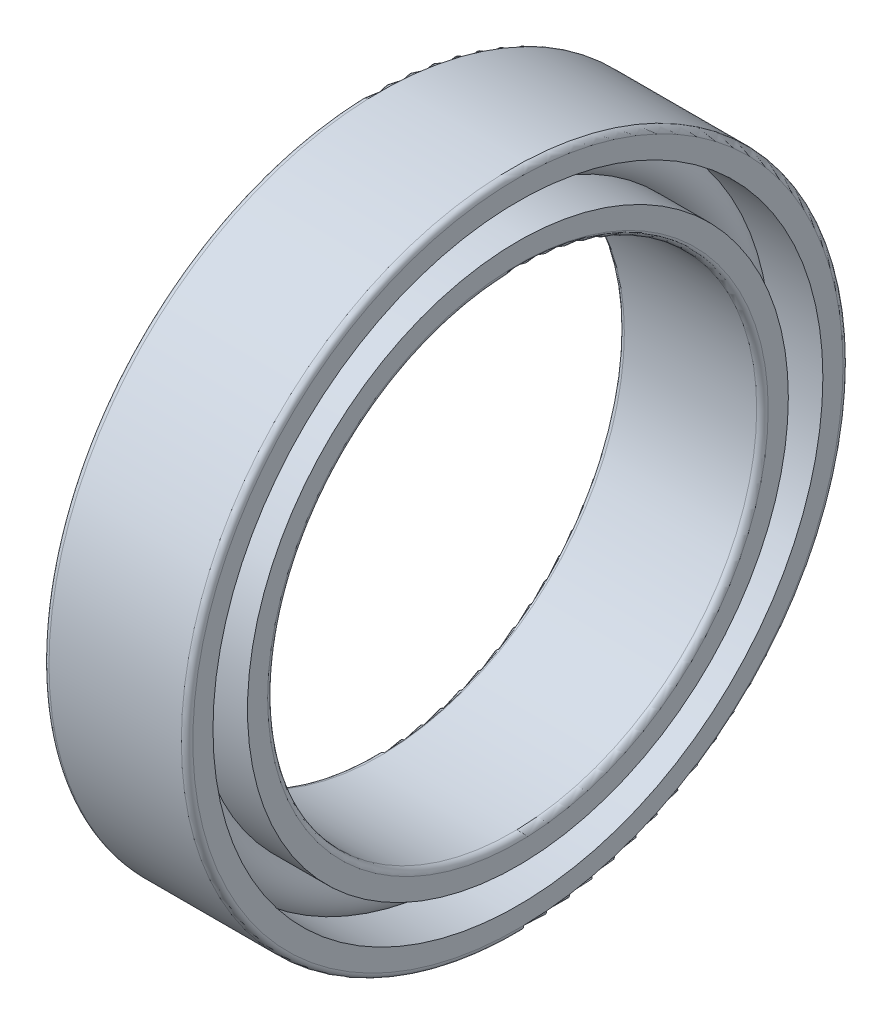
SolidWorks part; units mm, degrees
ref_plane "Plane1" through (0, 0, 0) normal (0, 0, 1) x (1, 0, 0)
ref_plane "Plane2" through (0, 0, 0) normal (0, 1, 0) x (1, 0, 0)
ref_plane "Plane3" through (0, 0, 0) normal (1, 0, 0) x (0, 0, -1)
other "Configuration Table"
sketch "Clipboard" plane through (0, 0, 0) normal (0, 0, 1) x (1, 0, 0)
  line L0 (-10, 0) -> (10, 0) construction
  line L1 (0, 0) -> (22.3471, -0.7804)
  line L2 (0, 0) -> (9.9939, 0.349)
  line L3 (0, 0) -> (22.3471, -0.7804)
  line L4 (0, 0) -> (-22.3573, -0.3902)
  dimension "BallCLRad" = 10
  dimension "Count" = 2
sketch "CagSpiSke" plane through (0, 0, 0) normal (0, 0, 1) x (1, 0, 0)
  line L0 (0.09, 9.85) -> (0.09, 10.15)
  line L1 (0.09, 10.15) -> (-0.09, 10.15)
  line L2 (-0.09, 10.15) -> (-0.09, 9.85)
  line L3 (-0.09, 9.85) -> (0.09, 9.85)
  line L4 (-20.6375, 0) -> (20.6375, 0) construction
  line L5 (0, 0) -> (0, 23.7692) construction
  dimension "OD" = 20.3
  dimension "ID" = 19.7
revolve "CageSpine" add sketch "CagSpiSke" angle 0.001 about L4 reverse direction yes
ref_axis "Axis1" through (-50, 0, 0) along (1, 0, 0)
sketch "CagBalSke" plane through (0, 0, 0) normal (0, 0, 1) x (1, 0, 0)
  line L0 (-0.99, 10) -> (0.99, 10)
  line L1 (-1.905, 10) -> (1.905, 10) construction
  line L2 (-10, 0) -> (10, 0) construction
  line L3 (0, 0) -> (0, 24) construction
  arc A0 (0.99, 10) -> (-0.99, 10) centre (0, 10) cw
  dimension "BallCLRad" = 10
revolve "CageBall" [suppressed] add sketch "CagBalSke" angle 360 about L1 reverse direction yes
pattern_circular "CageBalls" [suppressed] count 2 every 180 about axis through (-50, 0, 0) along (1, 0, 0)
sketch "CagTrmODSke" plane through (0, 0, 0) normal (0, 0, 1) x (1, 0, 0)
  line L0 (0.991, 10.15) -> (0.991, 10.991)
  line L1 (0.991, 10.991) -> (-0.991, 10.991)
  line L2 (-0.991, 10.991) -> (-0.991, 10.15)
  line L3 (-0.991, 10.15) -> (0.991, 10.15)
  line L4 (-20.6375, 0) -> (20.6375, 0) construction
  line L5 (0, 0) -> (0, 25) construction
  dimension "Width" = 1.982
  dimension "ID" = 20.3
  dimension "OD" = 21.982
revolve "CageTrimOD" [suppressed] cut sketch "CagTrmODSke" angle 360 about L4 reverse direction yes
sketch "CagTrmIDSke" plane through (0, 0, 0) normal (0, 0, 1) x (1, 0, 0)
  line L0 (0.991, 9.011) -> (0.991, 9.85)
  line L1 (0.991, 9.85) -> (-0.991, 9.85)
  line L2 (-0.991, 9.85) -> (-0.991, 9.011)
  line L3 (-0.991, 9.011) -> (0.991, 9.011)
  line L4 (-20.6375, 0) -> (20.6375, 0) construction
  line L5 (0, 0) -> (0, 25) construction
  dimension "Width" = 1.982
  dimension "ID" = 18.022
  dimension "OD" = 19.7
revolve "CageTrimID" [suppressed] cut sketch "CagTrmIDSke" angle 360 about L4 reverse direction yes
sketch "BalSimSke" plane through (0, 0, 0) normal (0, 0, 1) x (1, 0, 0)
  line L0 (-10, 0) -> (10, 0) construction
  line L1 (-10, 10) -> (10, 10) construction
  line L2 (0, 0) -> (0, 23) construction
  circle A0 centre (0, 10) radius 0.9
  dimension "BallCLRad" = 10
revolve "BallsSimplified" add sketch "BalSimSke" angle 360 about L0
sketch "BalDetSke" plane through (0, 0, 0) normal (0, 0, 1) x (1, 0, 0)
  line L0 (-0.9, 10) -> (0.9, 10)
  line L1 (-1.905, 10) -> (1.905, 10) construction
  line L2 (0, 0) -> (0, 25) construction
  arc A0 (0.9, 10) -> (-0.9, 10) centre (0, 10) cw
  dimension "BallCLRad" = 10
revolve "BallDetailed" [suppressed] add sketch "BalDetSke" angle 360 about L1 reverse direction yes
sketch "InnRacSke" plane through (0, 0, 0) normal (0, 0, 1) x (1, 0, 0)
  line L0 (-0.6369, 9.4) -> (-2.5, 9.4)
  line L1 (-2.5, 9.4) -> (-2.5, 8.7)
  line L2 (-2.3, 8.5) -> (2.3, 8.5)
  line L3 (2.5, 8.7) -> (2.5, 9.4)
  line L4 (2.5, 9.4) -> (0.6369, 9.4)
  line L5 (-20.6375, 0) -> (20.6375, 0) construction
  line L6 (0, 0) -> (0, 30) construction
  arc A0 (-2.5, 8.7) -> (-2.3, 8.5) centre (-2.3, 8.7) ccw
  arc A1 (2.3, 8.5) -> (2.5, 8.7) centre (2.3, 8.7) ccw
  arc A2 (0.6369, 9.4) -> (-0.6369, 9.4) centre (0, 10) cw
  dimension "BallCLRad" = 10
  dimension "Fillet_radius" = 0.2
  dimension "Ball_diameter" = 1.75
  dimension "ID" = 17
  dimension "OD" = 18.8
  dimension "Width" = 5
revolve "InnerRace" add sketch "InnRacSke" angle 360 about L5 reverse direction yes
sketch "OutRacSke" plane through (0, 0, 0) normal (0, 0, 1) x (1, 0, 0)
  line L0 (-0.6369, 10.6) -> (-2.5, 10.6)
  line L1 (-2.5, 10.6) -> (-2.5, 11.3)
  line L2 (-2.3, 11.5) -> (2.3, 11.5)
  line L3 (2.5, 11.3) -> (2.5, 10.6)
  line L4 (2.5, 10.6) -> (0.6369, 10.6)
  line L5 (-20.6375, 0) -> (20.6375, 0) construction
  line L6 (0, 0) -> (0, 30) construction
  arc A0 (-2.5, 11.3) -> (-2.3, 11.5) centre (-2.3, 11.3) cw
  arc A1 (2.3, 11.5) -> (2.5, 11.3) centre (2.3, 11.3) cw
  arc A2 (0.6369, 10.6) -> (-0.6369, 10.6) centre (0, 10) ccw
  dimension "BallCLRad" = 10
  dimension "Fillet_radius" = 0.2
  dimension "Ball_diameter" = 1.75
  dimension "Width" = 5
revolve "OuterRace" add sketch "OutRacSke" angle 360 about L5 reverse direction yes
pattern_circular "BallsDetailed" [suppressed] count 2 every 180 about axis through (-50, 0, 0) along (1, 0, 0)
equation "\"BallCLRad@Clipboard\" = ( \"OD@OutRacSke\" + \"ID@InnRacSke\" ) / 4"
equation "\"BallCLRad@BalSimSke\" = \"BallCLRad@Clipboard\""
equation "\"BallCLRad@BalDetSke\" = \"BallCLRad@Clipboard\""
equation "\"BallCLRad@InnRacSke\" = \"BallCLRad@Clipboard\""
equation "\"BallCLRad@OutRacSke\" = \"BallCLRad@Clipboard\""
equation "\"Ball_diameter@InnRacSke\" = \"Ball_diameter@BalDetSke\" - 0.05"
equation "\"Ball_diameter@OutRacSke\" = \"Ball_diameter@BalDetSke\" - 0.05"
equation "\"Ball_diameter@BalSimSke\" = \"Ball_diameter@BalDetSke\""
equation "\"Width@OutRacSke\" = \"Width@InnRacSke\""
equation "\"Fillet_radius@OutRacSke\" = \"Fillet_radius@InnRacSke\""
equation "\"Max_count@Clipboard\" = int( 3.14159265 / atn(( \"Ball_diameter@BalDetSke\" / 2) / sqr( \"BallCLRad@Clipboard\"  *  \"BallCLRad@Clipboard\" - ( \"Ball_diameter@BalDetSke\" / 2) *  ( \"Ball_diameter@BalDetSke\" / 2))))"
equation "\"Max_count@Clipboard\" = ((sgn( \"Max_count@Clipboard\" - \"Count@Clipboard\" )-1)*( \"Max_count@Clipboard\" - \"Count@Clipboard\" ))/-2+ \"Count@Clipboard\""
equation "\"Count@BallsDetailed\" = int( \"Show_count@Clipboard\" ) "
equation "\"Count@BallsDetailed\" = ((sgn( \"Count@BallsDetailed\" - \"Max_count@Clipboard\" )-1)*( \"Count@BallsDetailed\" - \"Max_count@Clipboard\" ))/-2+ \"Max_count@Clipboard\""
equation "\"Count@BallsDetailed\" = ((sgn( \"Count@BallsDetailed\" - \"Min_count@Clipboard\" )+1)*( \"Count@BallsDetailed\" - \"Min_count@Clipboard\"))/2 +\"Min_count@Clipboard\""
equation "\"Angle@BallsDetailed\" = 360.0 / \"Max_count@Clipboard\""
equation "\"BallCLRad@CagBalSke\" = \"BallCLRad@Clipboard\""
equation "\"Count@CageBalls\" = \"Count@BallsDetailed\""
equation "\"Angle@CageBalls\" = \"Angle@BallsDetailed\""
equation "\"Angle@CageSpine\" =  \"Angle@CageBalls\" * ( \"Count@CageBalls\" -1 + int( \"Count@CageBalls\" / \"Max_count@Clipboard\" ) )  + 0.001 -  int( \"Count@CageBalls\" / \"Max_count@Clipboard\" ) * 0.001"
equation "\"Angle@CageSpine\" =  \"Angle@CageSpine\" * int( \"Min_count@Clipboard\" / 2) + int(1 / \"Min_count@Clipboard\")  * 0.001"
equation "\"CageWallOD@CagBalSke\" =  \"Ball_diameter@BalDetSke\" * 1.1"
equation "\"Thickness@CagSpiSke\" =  \"Ball_diameter@BalDetSke\" * 0.1"
equation "\"OD@CagTrmODSke\" = \"BallCLRad@Clipboard\" * 2 + \"CageWallOD@CagBalSke\" + 0.002"
equation "\"ID@CagTrmODSke\" = \"BallCLRad@Clipboard\" * 2 + \"Ball_diameter@BalDetSke\" / 6"
equation "\"OD@CagTrmIDSke\" = \"BallCLRad@Clipboard\" * 2 - \"Ball_diameter@BalDetSke\" / 6"
equation "\"ID@CagTrmIDSke\" = \"BallCLRad@Clipboard\" * 2 - \"CageWallOD@CagBalSke\" + 0.002"
equation "\"OD@CagSpiSke\" = \"ID@CagTrmODSke\""
equation "\"ID@CagSpiSke\" = \"OD@CagTrmIDSke\""
equation "\"Width@CagTrmODSke\" = \"CageWallOD@CagBalSke\" + 0.002"
equation "\"Width@CagTrmIDSke\" = \"CageWallOD@CagBalSke\" + 0.002"
